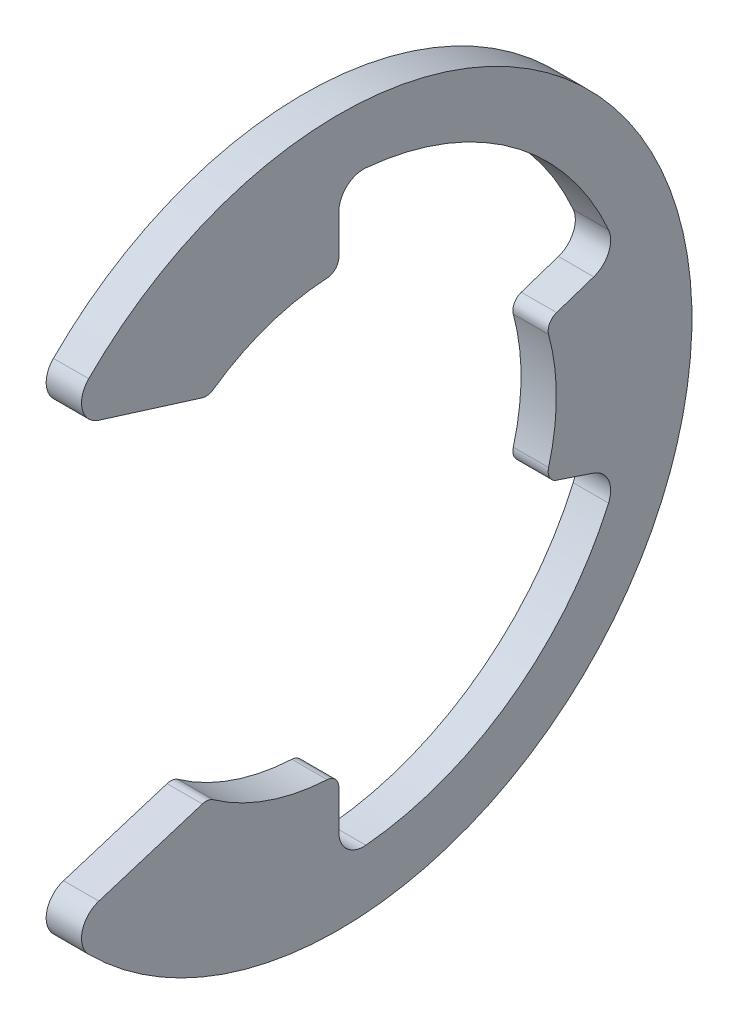
SolidWorks part; units mm, degrees
ref_plane "Front" through (0, 0, 0) normal (0, 0, 1) x (1, 0, 0)
ref_plane "Top" through (0, 0, 0) normal (0, 1, 0) x (1, 0, 0)
ref_plane "Right" through (0, 0, 0) normal (1, 0, 0) x (0, 0, -1)
sketch "Sketch1" plane through (0, 0, 0) normal (1, 0, 0) x (0, 0, -1)
  line L0 (-9.9448, -7.8988) -> (-4.6939, -6.2586)
  line L1 (-9.9448, 7.8988) -> (-4.6939, 6.2586)
  line L2 (0, -7.8232) -> (0, -10.5926)
  line L3 (0, 7.8232) -> (0, 10.5926)
  line L4 (7.4217, -2.4739) -> (10.049, -3.3497)
  line L5 (7.4217, 2.4739) -> (10.049, 3.3497)
  line L6 (0, 0) -> (-7.8232, 0) construction
  line L7 (7.4217, 2.4739) -> (7.4217, -2.4739) construction
  line L8 (0, -7.8232) -> (-4.6939, -6.2586) construction
  line L9 (0, 12.7) -> (0, -12.7) construction
  circle A2 centre (0, 0) radius 7.8232 construction
  arc A3 (-9.9448, -7.8988) -> (-9.9448, 7.8988) centre (0, 0) ccw
  arc A4 (-4.6939, -6.2586) -> (0, -7.8232) centre (0, 0) ccw
  arc A5 (-4.6939, 6.2586) -> (0, 7.8232) centre (0, 0) cw
  arc A6 (7.4217, 2.4739) -> (7.4217, -2.4739) centre (0, 0) cw
  arc A7 (0, -10.5926) -> (10.049, -3.3497) centre (0, 0) ccw
  arc A8 (10.049, 3.3497) -> (0, 10.5926) centre (0, 0) ccw
  point P8 (0, 7.8232)
  point P12 (0, 12.7)
  dimension "Free Diameter" = 15.6464
  dimension "D1" = 10.5926
  dimension "Ring OD" = 25.4
  dimension "D2" = 9.1486
  dimension "D10" = 12.5171
sketch "Sketch4" plane through (0, 0, 0) normal (0, 0, 1) x (1, 0, 0)
  line L0 (-0.635, 12.7) -> (0.635, 12.7) construction
  point P3 (0, 12.7)
  dimension "Ring Thickness" = 1.27
sketch "Sketch3" plane through (0, 0, 0) normal (1, 0, 0) x (0, 0, -1)
  line L6 (7.4217, -2.4739) -> (10.049, -3.3497)
  line L7 (0, -10.5926) -> (0, -7.8232)
  line L8 (-4.6939, -6.2586) -> (-9.9448, -7.8988)
  line L9 (-9.9448, 7.8988) -> (-4.6939, 6.2586)
  line L10 (0, 7.8232) -> (0, 10.5926)
  line L11 (10.049, 3.3497) -> (7.4217, 2.4739)
  line L12 (7.4217, -2.4739) -> (10.049, -3.3497)
  line L13 (0, -10.5926) -> (0, -7.8232)
  line L14 (-4.6939, -6.2586) -> (-9.9448, -7.8988)
  line L15 (-9.9448, 7.8988) -> (-4.6939, 6.2586)
  line L16 (0, 7.8232) -> (0, 10.5926)
  line L17 (10.049, 3.3497) -> (7.4217, 2.4739)
  arc A6 (0, -10.5926) -> (10.049, -3.3497) centre (0, 0) ccw
  arc A7 (-4.6939, -6.2586) -> (0, -7.8232) centre (0, 0) ccw
  arc A8 (-9.9448, -7.8988) -> (-9.9448, 7.8988) centre (0, 0) ccw
  arc A9 (0, 7.8232) -> (-4.6939, 6.2586) centre (0, 0) ccw
  arc A10 (10.049, 3.3497) -> (0, 10.5926) centre (0, 0) ccw
  arc A11 (7.4217, -2.4739) -> (7.4217, 2.4739) centre (0, 0) ccw
  arc A12 (0, -10.5926) -> (10.049, -3.3497) centre (0, 0) ccw
  arc A13 (-4.6939, -6.2586) -> (0, -7.8232) centre (0, 0) ccw
  arc A14 (-9.9448, -7.8988) -> (-9.9448, 7.8988) centre (0, 0) ccw
  arc A15 (0, 7.8232) -> (-4.6939, 6.2586) centre (0, 0) ccw
  arc A16 (10.049, 3.3497) -> (0, 10.5926) centre (0, 0) ccw
  arc A17 (7.4217, -2.4739) -> (7.4217, 2.4739) centre (0, 0) ccw
  dimension "D1" = 0
extrude "Boss-Extrude1" add sketch "Sketch3" along normal up to vertex (0.635 mm away) and the other way up to vertex (0.635 mm away) up to point (0.635, 12.7, 0) other way up to point (-0.635, 12.7, 0)
fillet "Fillet1" radius 0.889 6 edges at (0, -10.5926, 0) (0, -3.3497, -10.049) (0, 3.3497, -10.049) (0, 10.5926, 0) (0, -7.8988, 9.9448) (0, 7.8988, 9.9448)
fillet "Fillet2" radius 0.4445 6 edges at (0, -7.8232, 0) (0, -6.2586, 4.6939) (0, 2.4739, -7.4217) (0, -2.4739, -7.4217) (0, 6.2586, 4.6939) (0, 7.8232, 0)
equation "\"D1@Sketch1\" =  ( \"Ring OD@Sketch1\" + \"Free Diameter@Sketch1\" )  / 3.875"
equation "\"D10@Sketch1\"=\"Free Diameter@Sketch1\" * .8"
equation "\"D1@Fillet1\"=\"Ring Thickness@Sketch4\"*.7"
equation "\"D1@Fillet2\"=\"D1@Fillet1\"/2"
